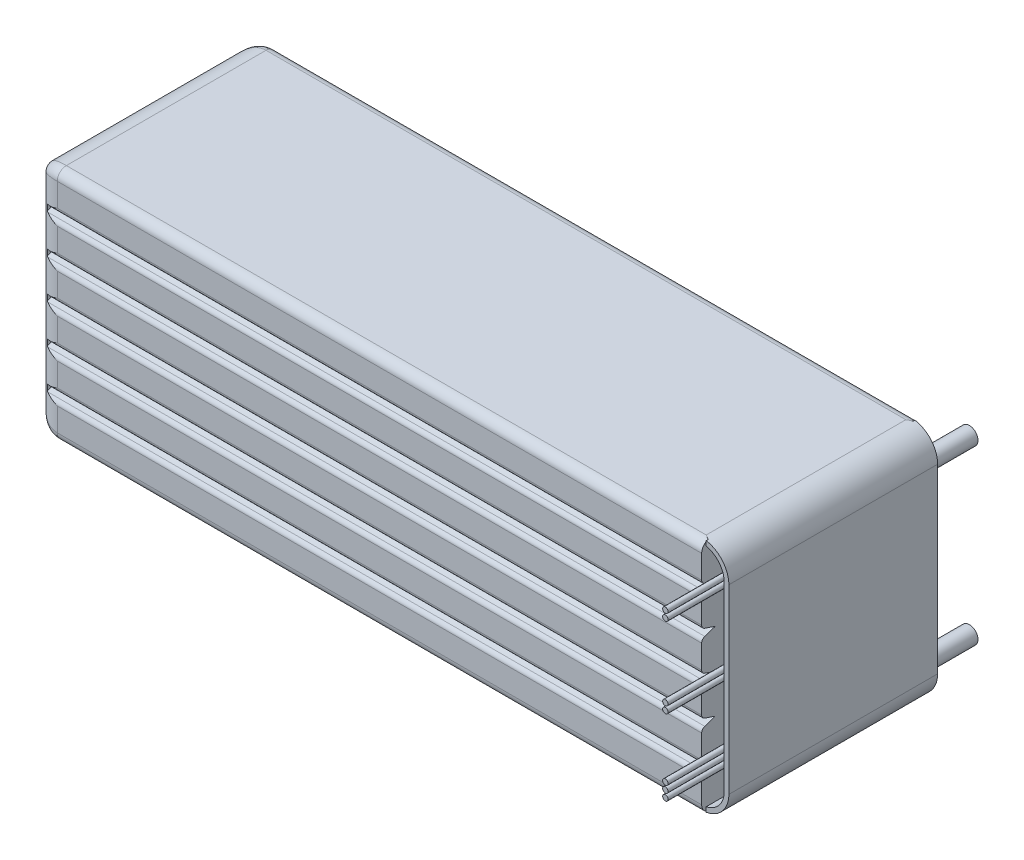
SolidWorks part; units mm, degrees
ref_plane "前视基准面" through (0, 0, 0) normal (0, 0, 1) x (1, 0, 0)
ref_plane "上视基准面" through (0, 0, 0) normal (0, 1, 0) x (1, 0, 0)
ref_plane "右视基准面" through (0, 0, 0) normal (1, 0, 0) x (0, 0, -1)
sketch "草图1" plane through (0, 0, 0) normal (0, 1, 0) x (1, 0, 0)
  line L1 (0, 0) -> (-148, 0)
  line L2 (0, 0) -> (0, 48)
  line L3 (0, 48) -> (-148, 48)
  line L4 (-148, 0) -> (-148, 48)
  line L5 (0, 0) -> (-148, 48) construction
  line L6 (0, 48) -> (-148, 0) construction
  point P4 (-74, 24)
  dimension "D1" = 148
  dimension "D2" = 48
extrude "凸台-拉伸1" add sketch "草图1" along normal blind 52
fillet "圆角1" radius 2 4 edges at (-74, 0, 0) (-74, 0, -48) (-74, 52, -48) (-74, 52, 0)
sketch "草图3" plane through (0, 0, 0) normal (1, 0, 0) x (0, 0, -1)
  line L1 (0, 50) -> (0, 2) construction
  line L4 (0, 35.5774) -> (3, 34.5774)
  line L5 (3, 34.5774) -> (0, 33.5774)
  line L6 (0, 33.5774) -> (0, 35.5774)
  line L7 (0, 27) -> (3, 26)
  line L8 (3, 26) -> (0, 25)
  line L9 (0, 25) -> (0, 27)
  line L10 (0, 18.4226) -> (3, 17.4226)
  line L11 (3, 17.4226) -> (0, 16.4226)
  line L12 (0, 16.4226) -> (0, 18.4226)
  line L13 (0, 9.8453) -> (3, 8.8453)
  line L14 (3, 8.8453) -> (0, 7.8453)
  line L15 (0, 7.8453) -> (0, 9.8453)
  line L16 (0, 44.1547) -> (3, 43.1547)
  line L17 (3, 43.1547) -> (0, 42.1547)
  line L18 (0, 42.1547) -> (0, 44.1547)
  line L19 (3, 8.8453) -> (3, 0.2679) construction
  line L20 (3, 8.8453) -> (3, 17.4226) construction
  line L21 (3, 26) -> (3, 17.4226) construction
  line L22 (3, 34.5774) -> (3, 26) construction
  line L23 (3, 26) -> (3, 34.5774) construction
  line L24 (3, 43.1547) -> (3, 34.5774) construction
  line L25 (3, 51.7321) -> (3, 43.1547) construction
  line L26 (24, 52) -> (24, 0) construction
  line L27 (2, 52) -> (46, 52) construction
  line L28 (2, 0) -> (46, 0) construction
  line L29 (45, 51.7321) -> (45, 43.1547) construction
  line L30 (45, 43.1547) -> (45, 34.5774) construction
  line L31 (45, 26) -> (45, 34.5774) construction
  line L32 (45, 34.5774) -> (45, 26) construction
  line L33 (45, 26) -> (45, 17.4226) construction
  line L34 (45, 8.8453) -> (45, 17.4226) construction
  line L35 (45, 8.8453) -> (45, 0.2679) construction
  line L36 (48, 42.1547) -> (48, 44.1547)
  line L37 (45, 43.1547) -> (48, 42.1547)
  line L38 (48, 44.1547) -> (45, 43.1547)
  line L39 (48, 7.8453) -> (48, 9.8453)
  line L40 (45, 8.8453) -> (48, 7.8453)
  line L41 (48, 9.8453) -> (45, 8.8453)
  line L42 (48, 16.4226) -> (48, 18.4226)
  line L43 (45, 17.4226) -> (48, 16.4226)
  line L44 (48, 18.4226) -> (45, 17.4226)
  line L45 (48, 25) -> (48, 27)
  line L46 (45, 26) -> (48, 25)
  line L47 (48, 27) -> (45, 26)
  line L48 (48, 33.5774) -> (48, 35.5774)
  line L49 (45, 34.5774) -> (48, 33.5774)
  line L50 (48, 35.5774) -> (45, 34.5774)
  arc A1 (0, 2) -> (2, 0) centre (2, 2) ccw construction
  arc A2 (2, 52) -> (0, 50) centre (2, 50) ccw construction
  dimension "D1" = 2
  dimension "D2" = 3
extrude "切除-拉伸1" cut sketch "草图3" against normal blind 145
fillet "圆角3" radius 1 20 edges at (-72.5, 7.8453, -48) (-72.5, 16.4226, -48) (-72.5, 9.8453, -48) (-72.5, 18.4226, -48) (-72.5, 25, -48) (-72.5, 27, -48) (-72.5, 33.5774, -48) (-72.5, 35.5774, -48) (-72.5, 42.1547, -48) (-72.5, 44.1547, -48) (-72.5, 7.8453, 0) (-72.5, 9.8453, 0) (-72.5, 16.4226, 0) (-72.5, 18.4226, 0) (-72.5, 25, 0) (-72.5, 27, 0) (-72.5, 33.5774, 0) (-72.5, 35.5774, 0) (-72.5, 42.1547, 0) (-72.5, 44.1547, 0)
ref_plane "基准面1" through (0, 0, -24) normal (0, 0, -1) x (-1, 0, 0)
sketch "草图5" plane through (0, 0, -24) normal (0, 0, -1) x (-1, 0, 0)
  line L2 (-5, 52) -> (-5, 0)
  line L5 (0, 52) -> (-5, 52)
  line L6 (0, 52) -> (0, 0)
  line L7 (0, 0) -> (-5, 0)
  point P0 (-5, 0.2135)
  dimension "D1" = 5
extrude "凸台-拉伸3" add sketch "草图5" along normal mid plane 46
fillet "圆角4" radius 6 2 edges at (5, 0, -24) (5, 52, -24)
sketch "草图7" plane through (0, 0, -47) normal (0, 0, -1) x (-1, 0, 0)
  line L0 (0, 50.899) -> (0, 1.101)
  line L1 (0, 43.8214) -> (0, 51.7321) construction
  line L2 (0, 50) -> (0, 44.8755) construction
  line L3 (0, 0.2679) -> (0, 8.1786) construction
  line L4 (-4, 6) -> (-4, 46)
  line L5 (-5, 46) -> (-5, 6) construction
  arc A0 (-4, 46) -> (0, 50.899) centre (1, 46) cw
  arc A1 (-4, 6) -> (0, 1.101) centre (1, 6) ccw
  point P14 (0, 0)
  point P16 (0, 0)
  dimension "D1" = 1
extrude "切除-拉伸2" cut sketch "草图7" against normal blind 5
sketch "草图8" plane through (0, 0, -1) normal (0, 0, 1) x (1, 0, 0)
  line L0 (0, 50.866) -> (0, 1.134)
  line L1 (0, 50) -> (0, 51.7321) construction
  line L2 (0, 0.2679) -> (0, 2) construction
  line L3 (3.9677, 6) -> (3.9677, 46)
  line L4 (5, 46) -> (5, 6) construction
  arc A0 (0, 50.866) -> (3.9677, 46) centre (-1, 46) cw
  arc A1 (3.9677, 6) -> (0, 1.134) centre (-1, 6) cw
  point P14 (0, 0)
  point P17 (5, 40.0291)
  dimension "D1" = 1.0323
extrude "切除-拉伸3" cut sketch "草图8" against normal blind 5
sketch "草图9" plane through (0, 0, -42) normal (0, 0, -1) x (-1, 0, 0)
  line L0 (1, 52) -> (148, 52) construction
  line L1 (148, 0) -> (1, 0) construction
  line L2 (-2, 45) -> (-2, 7) construction
  line L3 (-4, 46) -> (-4, 6) construction
  circle A0 centre (-2, 45) radius 1.9
  circle A1 centre (-2, 7) radius 1.9
  dimension "D2" = 7
  dimension "D4" = 3.8
  dimension "D1" = 7
  dimension "D3" = 2
extrude "凸台-拉伸8" add sketch "草图9" along normal blind 15
sketch "草图10" plane through (0, 0, -6) normal (0, 0, 1) x (1, 0, 0)
  line L0 (1, 44.1547) -> (1, 43.5547) construction
  line L1 (1, 43.5547) -> (1, 26.5) construction
  line L2 (1, 26.5) -> (1, 25) construction
  line L3 (1, 25) -> (1, 8.6664) construction
  line L4 (1, 8.6664) -> (1, 8.3453) construction
  line L5 (0, 17.4226) -> (0, 18.1947) construction
  line L7 (-145, 43.1547) -> (0, 43.1547) construction
  line L8 (-145, 26) -> (0, 26) construction
  line L9 (-145, 8.8453) -> (0, 8.8453) construction
  circle A0 centre (1, 44.1547) radius 0.6
  circle A2 centre (1, 26.5) radius 0.6
  circle A3 centre (1, 25) radius 0.6
  circle A5 centre (1, 8.3453) radius 0.6
  circle A6 centre (1, 9.8453) radius 0.6
  circle A7 centre (1, 42.6547) radius 0.6
  circle A8 centre (1, 11.3453) radius 0.6
  dimension "D2" = 1.2
  dimension "D3" = 1.5
  dimension "D4" = 1.5
  dimension "D5" = 1
  dimension "D6" = 1.5
  dimension "D9" = 1.5
  dimension "D1" = 1
  dimension "D7" = 1
  dimension "D8" = 1
extrude "凸台-拉伸9" add sketch "草图10" along normal blind 15
fillet "圆角5" radius 6 8 edges at (-148, 51.4142, -0.5858) (-148, 52, -24) (-148, 51.4142, -47.4142) (-148, 26, -48) (-148, 0.5858, -47.4142) (-148, 0, -24) (-148, 0.5858, -0.5858) (-148, 26, 0)
